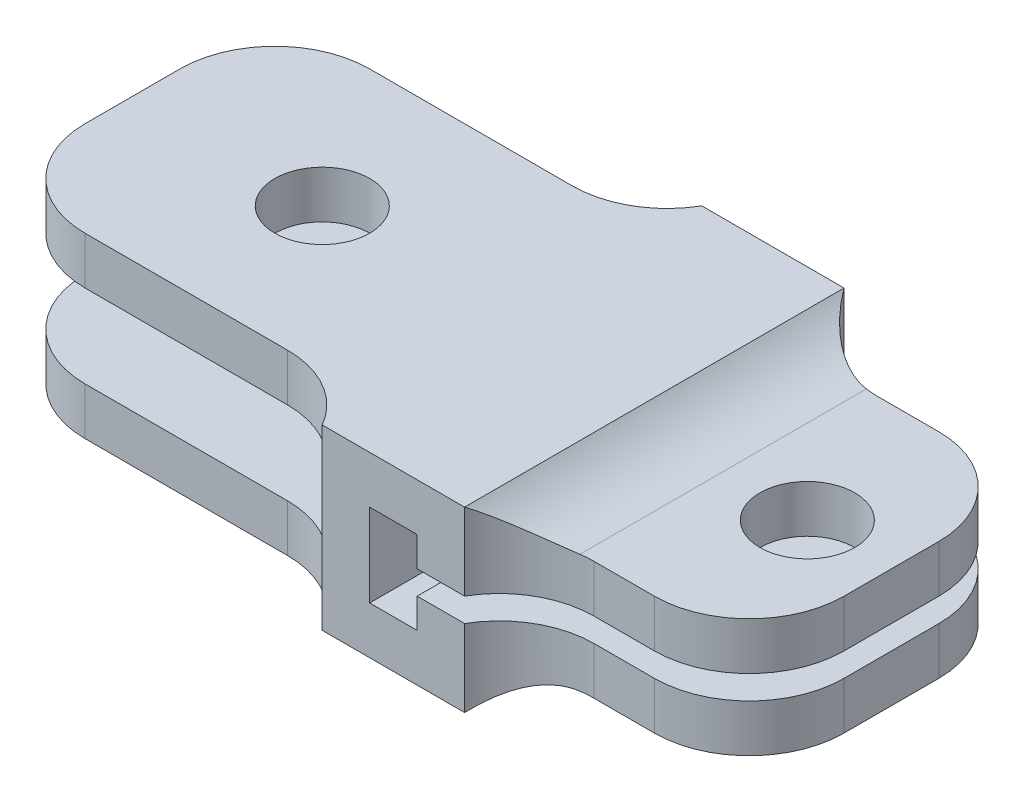
SolidWorks part; units mm, degrees
ref_plane "Piano frontale" through (0, 0, 0) normal (0, 0, 1) x (1, 0, 0)
ref_plane "Piano superiore" through (0, 0, 0) normal (0, 1, 0) x (1, 0, 0)
ref_plane "Piano destro" through (0, 0, 0) normal (1, 0, 0) x (0, 0, -1)
sketch "Schizzo1" plane through (0, 0, 0) normal (0, 0, 1) x (1, 0, 0)
  line L0 (-7.5, 9.375) -> (7.5, 9.375)
  line L1 (-2.5, -4.375) -> (2.5, -4.375)
  line L2 (-2.5, -4.375) -> (-2.5, 4.375)
  line L3 (-2.5, 4.375) -> (2.5, 4.375)
  line L4 (2.5, -4.375) -> (2.5, 4.375)
  line L5 (-2.5, -4.375) -> (2.5, 4.375) construction
  line L6 (-2.5, 4.375) -> (2.5, -4.375) construction
  line L7 (7.5, -9.375) -> (7.5, 9.375)
  line L8 (-7.5, -9.375) -> (7.5, -9.375)
  line L9 (-7.5, -9.375) -> (-7.5, 9.375)
  point P0 (0, 0)
  dimension "D1" = 8.75
  dimension "D2" = 5
  dimension "D3" = 5
extrude "Estrusione-Estrusione1" add sketch "Schizzo1" along normal blind 40
sketch "Schizzo2" plane through (0, 0, 40) normal (0, 0, 1) x (1, 0, 0)
  line L0 (2.5, 0) -> (7.5, 0) construction
  line L1 (2.5, -4.375) -> (2.5, 4.375) construction
  line L2 (7.5, -9.375) -> (7.5, 9.375) construction
  line L4 (2.5, -1.25) -> (7.5, -1.25)
  line L5 (2.5, -1.25) -> (2.5, 1.25)
  line L6 (2.5, 1.25) -> (7.5, 1.25)
  line L7 (7.5, -1.25) -> (7.5, 1.25)
  line L8 (2.5, -1.25) -> (7.5, 1.25) construction
  line L9 (2.5, 1.25) -> (7.5, -1.25) construction
  point P6 (5, 0)
  dimension "D1" = 2.5
extrude "Taglio-Estrusione1" cut sketch "Schizzo2" against normal through all both
sketch "Schizzo4" plane through (-7.5, 0, 0) normal (-1, 0, 0) x (0, 0, 1)
  line L0 (0, 0) -> (40, 0) construction
  line L1 (40, 9.375) -> (40, -9.375) construction
  line L2 (40, 9.375) -> (0, 9.375) construction
  line L3 (5, 9.375) -> (35, 9.375)
  line L4 (5, 9.375) -> (5, 4.375)
  line L5 (5, 4.375) -> (35, 4.375)
  line L6 (35, 9.375) -> (35, 4.375)
  line L7 (0, 9.375) -> (0, -9.375) construction
  line L8 (35, -9.375) -> (35, -4.375)
  line L9 (5, -4.375) -> (35, -4.375)
  line L10 (5, -9.375) -> (35, -9.375)
  line L11 (5, -9.375) -> (5, -4.375)
  dimension "D1" = 5
  dimension "D2" = 5
  dimension "D3" = 5
extrude "Estrusione-Estrusione2" add sketch "Schizzo4" along normal blind 40
fillet "Raccordo1" radius 10 4 edges at (-47.5, 6.875, 5) (-47.5, 6.875, 35) (-47.5, -6.875, 5) (-47.5, -6.875, 35)
sketch "Schizzo5" plane through (7.5, 0, 0) normal (1, 0, 0) x (0, 0, -1)
  line L0 (0, 1.25) -> (-40, 1.25) construction
  line L1 (-35, 1.25) -> (-5, 1.25)
  line L2 (-35, 1.25) -> (-35, 6.25)
  line L3 (-35, 6.25) -> (-5, 6.25)
  line L4 (-5, 1.25) -> (-5, 6.25)
  line L5 (-40, 1.25) -> (-40, 9.375) construction
  line L6 (0, 1.25) -> (0, 9.375) construction
  line L7 (-40, 0) -> (0, 0) construction
  line L8 (-40, 4.375) -> (-40, -4.375) construction
  line L9 (-35, -1.25) -> (-35, -6.25)
  line L10 (-35, -6.25) -> (-5, -6.25)
  line L11 (-35, -1.25) -> (-5, -1.25)
  line L12 (-5, -1.25) -> (-5, -6.25)
  dimension "D1" = 5
  dimension "D2" = 5
  dimension "D3" = 5
extrude "Estrusione-Estrusione3" add sketch "Schizzo5" along normal blind 25
fillet "Raccordo2" radius 10 4 edges at (32.5, 3.75, 35) (32.5, -3.75, 35) (32.5, 3.75, 5) (32.5, -3.75, 5)
fillet "Raccordo3" radius 10 4 edges at (7.5, -3.75, 5) (7.5, 3.75, 5) (7.5, -3.75, 35) (7.5, 3.75, 35)
fillet "Raccordo4" radius 10 2 edges at (7.5, -6.25, 20) (7.5, 6.25, 20)
fillet "Raccordo5" radius 10 4 edges at (-7.5, 6.875, 35) (-7.5, 6.875, 5) (-7.5, -6.875, 5) (-7.5, -6.875, 35)
sketch "Schizzo6" plane through (0, 6.25, 0) normal (0, 1, 0) x (1, 0, 0)
  line L0 (14.7618, -20) -> (32.5, -20) construction
  line L1 (14.7618, -4.9017) -> (14.7618, -35.0983) construction
  line L2 (32.5, -15) -> (32.5, -25) construction
  circle A0 centre (23.6309, -20) radius 5
  point P8 (-16.2885, -36.8689)
  dimension "D1" = 10
sketch "Schizzo7" plane through (0, 9.375, 0) normal (0, 1, 0) x (1, 0, 0)
  line L0 (-7.5, -40) -> (-7.5, 0) construction
  line L1 (7.5, 0) -> (-7.5, 0) construction
  line L2 (-7.5, -20) -> (-47.5, -20) construction
  line L3 (-47.5, -25) -> (-47.5, -15) construction
  circle A0 centre (-27.5, -20) radius 5
  dimension "D1" = 10
extrude "Taglio-Estrusione2" cut sketch "Schizzo6" against normal through all both
extrude "Taglio-Estrusione3" cut sketch "Schizzo7" against normal through all both
